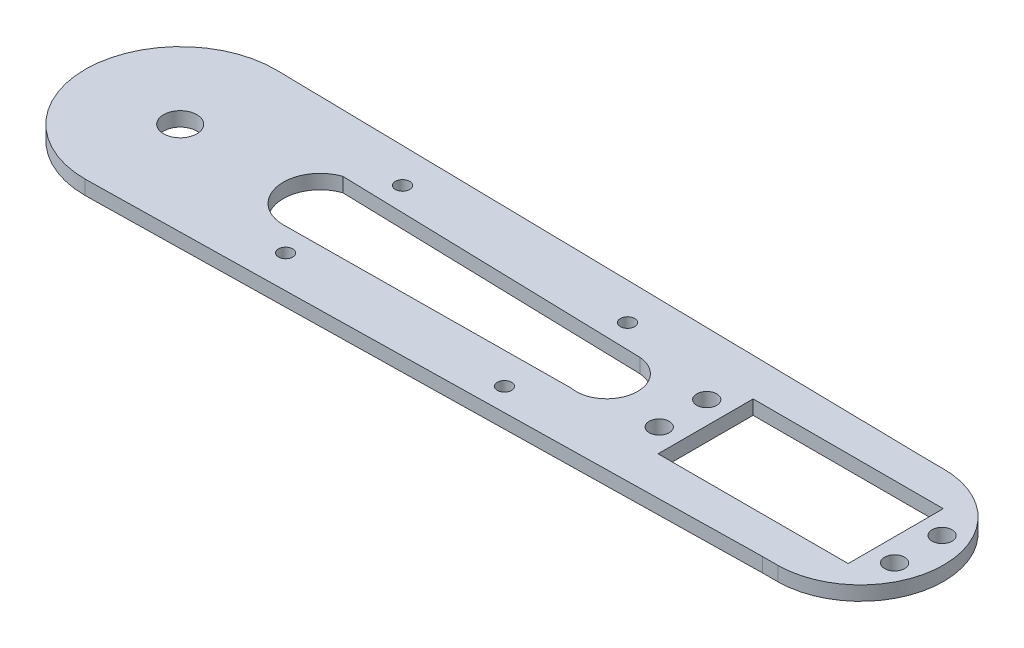
SolidWorks part; units mm, degrees
ref_plane "Front Plane" through (0, 0, 0) normal (0, 0, 1) x (1, 0, 0)
ref_plane "Top Plane" through (0, 0, 0) normal (0, 1, 0) x (1, 0, 0)
ref_plane "Right Plane" through (0, 0, 0) normal (1, 0, 0) x (0, 0, -1)
sketch "Sketch1" plane through (0, 0, 0) normal (0, 1, 0) x (1, 0, 0)
  line L0 (0.3571, 19.9968) -> (140.3125, 17.4972)
  line L1 (140, -17.5) -> (0, -20)
  circle A0 centre (0, 0) radius 20
  circle A1 centre (140, 0) radius 17.5
  point P11 (70.9941, 1.1797)
  dimension "D1" = 140
  dimension "D2" = 40
  dimension "D3" = 35
extrude "Boss-Extrude1" add sketch "Sketch1" along normal blind 3 contours L1 A0 | A1 L0 A0 L1 | A1 A0 region at (70.0919, 0, -0.0019) region at (0, 0, 0) region at (140, 0, 0)
sketch "Sketch2" plane through (0, 3, 0) normal (0, 1, 0) x (1, 0, 0)
  line L1 (123.5, 6) -> (146, 6)
  line L2 (123.5, 6) -> (123.5, -6)
  line L3 (123.5, -6) -> (146, -6)
  line L4 (146, 6) -> (146, -6)
  circle A0 centre (0, 0) radius 3.5
  circle A1 centre (140, 0) radius 3.5
  circle A2 centre (148.6, 0) radius 1
  circle A3 centre (120.9, 0) radius 1
  point P15 (146, 0)
  dimension "D1" = 7
  dimension "D2" = 7
  dimension "D3" = 2
  dimension "D6" = 27.7
  dimension "D7" = 2.6
  dimension "D8" = 8.6
  dimension "D4" = 12
  dimension "D5" = 22.5
extrude "Cut-Extrude1" cut sketch "Sketch2" against normal through all
sketch "Sketch4" plane through (0, 3, 0) normal (0, 1, 0) x (1, 0, 0)
  line L0 (90.8922, 5.8871) -> (26.5844, 7.6174)
  line L1 (29.1576, -7.4774) -> (89.1576, -6.9485)
  circle A2 centre (0, 0) radius 3.2414
  arc A6 (26.5844, 7.6174) -> (29.1576, -7.4774) centre (29.1653, 0.2906) ccw
  arc A7 (90.8922, 5.8871) -> (89.1576, -6.9485) centre (90.324, -0.5711) cw
  dimension "D2" = 7.768
  dimension "D3" = 6.4832
  dimension "D1" = 60
  dimension "D4" = 2.046
  dimension "D5" = 29.1653
extrude "Cut-Extrude3" cut sketch "Sketch4" against normal through all contours A7 L0 A6 L1 | A7 L0 A6 L1 region at (58.1028, 3, 0.2143)
sketch "Sketch8" plane through (0, 3, 0) normal (0, 1, 0) x (1, 0, 0)
  circle A0 centre (0, 0) radius 1.5
  circle A1 centre (140, 0) radius 3.5
  dimension "D1" = 3
  dimension "D2" = 7
extrude "Cut-Extrude6" cut sketch "Sketch8" against normal through all rebuild error yes
sketch "Sketch9" plane through (0, 3, 0) normal (0, 1, 0) x (1, 0, 0)
  circle A0 centre (140, 0) radius 4.4965
extrude "Cut-Extrude7" cut sketch "Sketch9" against normal blind 10
sketch "Sketch10" plane through (0, 3, 0) normal (0, 1, 0) x (1, 0, 0)
  line L0 (70.9941, 1.1797) -> (70.9941, 35.0995) construction
  line L1 (58.7383, 6.7522) -> (59.2603, 26.1531) construction
  line L3 (90.8922, 5.8871) -> (26.5844, 7.6174) construction
  circle A4 centre (34.5417, 12.2315) radius 1.5
  circle A5 centre (34.5417, -12.3733) radius 1.5
  circle A6 centre (81.8715, -13.6467) radius 1.5
  circle A7 centre (83.1946, 10.9224) radius 1.5
  dimension "D2" = 24.3353
  dimension "D3" = 3
  dimension "D4" = 3
  dimension "D1" = 3
  dimension "D5" = 3
extrude "Cut-Extrude8" cut sketch "Sketch10" against normal blind 10
sketch "Sketch11" plane through (0, 3, 0) normal (0, 1, 0) x (1, 0, 0)
  line L0 (140, 0) -> (144.131, 0) construction
  line L1 (150.32, 10.2219) -> (110.32, 10.2219)
  line L2 (150.32, 10.2219) -> (150.32, -9.7781)
  line L3 (150.32, -9.7781) -> (110.32, -9.7781)
  line L4 (110.32, 10.2219) -> (110.32, -9.7781)
  line L5 (150.32, -9.7781) -> (110.32, 10.2219) construction
  line L6 (110.32, -9.7781) -> (150.32, 10.2219) construction
  line L7 (130.32, 0.2219) -> (130.32, 6) construction
  line L8 (123.5, 6) -> (146, 6) construction
  circle A0 centre (140, 0) radius 3.5 construction
  circle A1 centre (155.08, 5.2219) radius 2.1
  circle A2 centre (155.08, -4.7781) radius 2.1
  circle A3 centre (105.56, -4.7781) radius 2.1
  circle A4 centre (105.56, 5.2219) radius 2.1
  point P9 (130.32, 0.2219)
  dimension "D4" = 4.2
  dimension "D5" = 4.76
  dimension "D6" = 5
  dimension "D7" = 10
  dimension "D1" = 9.68
  dimension "D2" = 40
  dimension "D3" = 20
extrude "Cut-Extrude9" cut sketch "Sketch11" against normal blind 10
sketch "Sketch12" plane through (0, 3, 0) normal (0, 1, 0) x (1, 0, 0)
  line L0 (140.3125, 17.4972) -> (142.8697, 17.4972)
  line L1 (150.3336, 14.1233) -> (150.3336, -14.1233)
  line L2 (143.3011, -17.5) -> (140, -17.5)
  arc A0 (142.8697, 17.4972) -> (143.3011, -17.5) centre (143.1334, -0.0008) cw
  arc A1 (155.9881, 7.1154) -> (156.9646, 4.2955) centre (155.08, 5.2219) ccw construction
  arc A2 (155.9881, 7.1154) -> (156.9646, 4.2955) centre (155.08, 5.2219) ccw
  arc A3 (157.0344, -4.0098) -> (156.2354, -6.5317) centre (155.08, -4.7781) ccw construction
  arc A4 (157.0344, -4.0098) -> (156.2354, -6.5317) centre (155.08, -4.7781) ccw
  circle A5 centre (155.08, 5.2219) radius 2.1
  circle A6 centre (155.08, -4.7781) radius 2.1
  circle A7 centre (140, 0) radius 17.5 construction
  arc A8 (140, -17.5) -> (150.3336, -14.1233) centre (140, 0) ccw
  arc A9 (150.3336, 14.1233) -> (140.3125, 17.4972) centre (140, 0) ccw
  arc M4 (156.2354, -6.5317) -> (157.0344, -4.0098) centre (155.08, -4.7781) cw
  arc M5 (157.0344, -4.0098) -> (156.9646, 4.2955) centre (140, 0) ccw
  arc M6 (156.9646, 4.2955) -> (155.9881, 7.1154) centre (155.08, 5.2219) cw
  arc M7 (155.9881, 7.1154) -> (140.3125, 17.4972) centre (140, 0) ccw
  arc M11 (140, -17.5) -> (156.2354, -6.5317) centre (140, 0) ccw
  dimension "D1" = 17.5
extrude "Boss-Extrude3" add sketch "Sketch12" against normal blind 3 contours A6 L2 A0 L0 A5 M11 M7 M5 | L1 M7 M11 M4 M5 M6 region at (141.5911, 3, -17.4566) region at (152.8795, 3, 0.0303)
sketch "Sketch13" plane through (0, 3, 0) normal (0, 1, 0) x (1, 0, 0)
  line L0 (140, 0) -> (160.632, 0.2149)
  arc A0 (143.3011, -17.5) -> (142.8697, 17.4972) centre (143.1334, -0.0008) ccw construction
  dimension "D1" = 20.6332
sketch "Sketch14" plane through (0, 3, 0) normal (0, 1, 0) x (1, 0, 0)
  line L0 (140, 0) -> (160.632, 0.2149)
  dimension "D1" = 20.632
